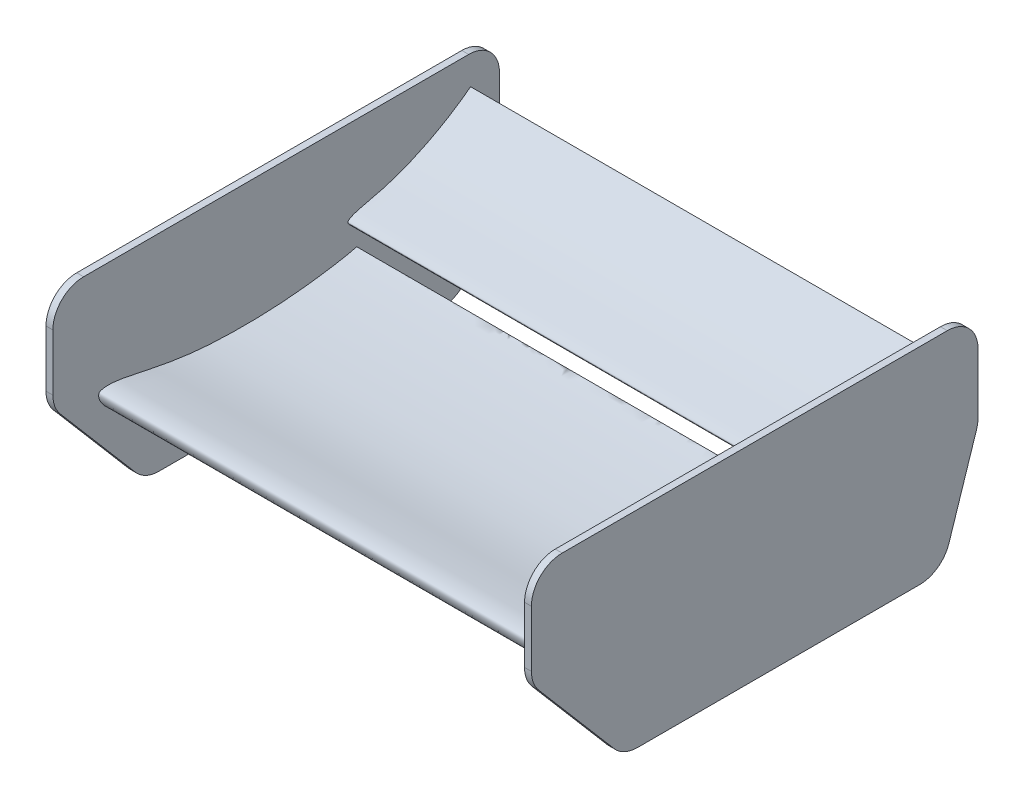
SolidWorks part; units mm, degrees
ref_plane "Front Plane" through (0, 0, 0) normal (0, 0, 1) x (1, 0, 0)
ref_plane "Top Plane" through (0, 0, 0) normal (0, 1, 0) x (1, 0, 0)
ref_plane "Right Plane" through (0, 0, 0) normal (1, 0, 0) x (0, 0, -1)
ref_plane "Soft Top Limit" through (0, 1174.6, 0) normal (0, 1, 0) x (1, 0, 0)
ref_plane "Soft Rear Limit" through (0, 0, -1192.975) normal (0, 0, 1) x (1, 0, 0)
ref_plane "Soft Right Limit" through (-501.65, 0, 0) normal (1, 0, 0) x (0, 0, -1)
ref_plane "Soft Left Limit" through (501.65, 0, 0) normal (1, 0, 0) x (0, 0, -1)
ref_plane "Soft Front Limit" through (0, 0, -165.1) normal (0, 0, 1) x (1, 0, 0)
ref_plane "Slant Limit" through (0, 528.6251, -619.2711) normal (0, -0.6492, 0.7606) x (1, 0, 0)
ref_plane "Bottom" through (0, 476.25, 0) normal (0, 1, 0) x (1, 0, 0)
ref_plane "Midplane" through (0, 0, 0) normal (1, 0, 0) x (0, 0, -1)
curve "Imported Airfoil Curve"
  spline degree 3 poles (0, 2520.0207, 6.126) (0, 2544.889, -1.81) (0, 2521.8965, 7.8839) (0, 2505.3253, 17.7145) (0, 2467.7144, 38.5723) (0, 2424.2142, 62.3813) (0, 2368.0949, 87.8078) (0, 2301.3729, 113.3478) (0, 2223.8362, 140.5377) (0, 2136.6129, 169.2441) (0, 2040.932, 199.097) (0, 1938.2341, 229.6055) (0, 1829.9414, 260.0781) (0, 1717.5266, 289.8586) (0, 1602.4273, 318.1375) (0, 1486.0259, 343.9752) (0, 1369.6902, 366.5754) (0, 1254.3666, 384.7865) (0, 1140.5393, 397.0034) (0, 1028.6357, 403.0127) (0, 919.0585, 402.9406) (0, 812.3986, 397.0375) (0, 709.2785, 385.5985) (0, 610.4299, 369.039) (0, 516.5862, 348.1086) (0, 428.5874, 323.3415) (0, 347.2653, 295.2055) (0, 273.332, 264.2656) (0, 207.4209, 231.0894) (0, 150.0337, 196.3024) (0, 101.596, 160.572) (0, 62.3674, 124.65) (0, 32.4977, 89.3959) (0, 12.0597, 55.6746) (0, 1.683, 26.6201) (0, -0.5567, 6.5526) (0, 0.5894, -3.9947) (0, 1.6947, -9.1451) (0, 2.8711, -12.4915) (0, 3.9449, -14.9776) (0, 4.8993, -16.669) (0, 5.9763, -18.2433) (0, 7.3264, -19.6365) (0, 8.8595, -20.9434) (0, 11.1868, -22.7306) (0, 14.6073, -24.7406) (0, 20.085, -27.4067) (0, 26.8353, -29.9257) (0, 44.6446, -35.1819) (0, 77.8093, -38.8998) (0, 130.2841, -38.2927) (0, 196.3018, -31.4611) (0, 276.2192, -18.4434) (0, 370.8288, 0.8611) (0, 480.7331, 24.811) (0, 605.9792, 50.0099) (0, 745.0759, 74.1542) (0, 895.4497, 95.0846) (0, 1053.6786, 110.004) (0, 1215.6439, 118.3392) (0, 1377.6893, 121.6348) (0, 1537.1174, 120.5125) (0, 1691.5141, 115.2051) (0, 1838.3121, 105.7388) (0, 1975.028, 93.0069) (0, 2099.5942, 78.4581) (0, 2210.5746, 63.1262) (0, 2306.3634, 48.0168) (0, 2387.2069, 33.7158) (0, 2449.0745, 22.0129) (0, 2499.1865, 10.4993) (0, 2520.0207, 6.126) (0, 2544.889, -1.81) (0, 2521.8965, 7.8839) knots -0.016237 -0.007308 -0.001841 0 0.001813 0.006911 0.014576 0.024172 0.035572 0.049013 0.064513 0.081849 0.100772 0.120997 0.142228 0.164173 0.186537 0.209023 0.231367 0.25332 0.274804 0.295858 0.316449 0.336531 0.356033 0.374893 0.39299 0.410197 0.426388 0.441459 0.455334 0.467938 0.479236 0.489204 0.497851 0.505194 0.511308 0.515097 0.516441 0.517273 0.51806 0.518436 0.518797 0.519154 0.519508 0.519887 0.520289 0.52116 0.522116 0.52372 0.525214 0.532575 0.542381 0.554776 0.569931 0.588005 0.609188 0.633329 0.660001 0.688743 0.718873 0.749543 0.780127 0.810209 0.839387 0.867183 0.893104 0.91676 0.937874 0.956199 0.971544 0.983763 0.992692 0.998159 1 1.001813 1.006911 1.014576 periodic
sketch "Airfoils Sketch" plane through (0, 0, 0) normal (1, 0, 0) x (0, 0, -1)
  line L0 (165.1, 1174.6) -> (165.1, 1060.6753) construction
  line L1 (165.1, 1060.6753) -> (663.9798, 476.25) construction
  line L2 (663.9798, 476.25) -> (1192.975, 476.25) construction
  line L3 (1192.975, 476.25) -> (1192.975, 1174.6) construction
  line L4 (1192.975, 1174.6) -> (165.1, 1174.6) construction
  line L5 (509.9361, 1174.6) -> (-509.9361, 1174.6) construction
  line L6 (165.1, 67.0076) -> (165.1, -67.0076) construction
  line L7 (364.7288, 826.8151) -> (873.8134, 230.4351) construction
  line L8 (279.3831, 476.25) -> (-279.3831, 476.25) construction
  line L9 (1192.975, 353.2696) -> (1192.975, -353.2696) construction
  line L10 (364.5896, 498.1423) -> (364.5896, 1393.8577) construction
  line L11 (897.9896, 508.5908) -> (897.9896, 1383.4092) construction
  line L12 (897.9896, 946) -> (364.5896, 946) construction
  line L13 (262.9896, 946) -> (1192.975, 946) construction
  line L14 (855.8887, 1048.5614) -> (904.1623, 945.0386) construction
  line L15 (1108.8736, 1167.1505) -> (1157.6222, 1062.6086) construction
  line L16 (1133.2479, 1114.8795) -> (880.0255, 996.8) construction
  line L17 (219.6255, 996.8) -> (1192.975, 996.8) construction
  line L21 (176.2614, 1047.6) -> (1192.975, 1047.6) construction
  spline S0 degree 3 poles (893.7912, 944.7229) (899.0172, 946.3778) (894.1843, 944.3529) (890.6998, 942.2962) (882.7919, 937.9336) (873.6459, 932.9541) (861.8492, 927.6408) (847.826, 922.3086) (831.5308, 916.6349) (813.2009, 910.6474) (793.0943, 904.4229) (771.5139, 898.0641) (748.7586, 891.7155) (725.138, 885.5141) (700.9544, 879.6292) (676.4985, 874.2577) (652.0578, 869.5659) (627.8318, 865.7954) (603.9228, 863.283) (580.4206, 862.0732) (557.4098, 862.1394) (535.0144, 863.4287) (513.3649, 865.8789) (492.6147, 869.4025) (472.9176, 873.8415) (454.4497, 879.0835) (437.3855, 885.0299) (421.8742, 891.5616) (408.0485, 898.5592) (396.0136, 905.8911) (385.8586, 913.417) (377.6374, 920.9787) (371.3813, 928.3959) (367.1052, 935.4868) (364.9396, 941.5929) (364.4786, 945.8081) (364.7242, 948.0225) (364.9587, 949.1035) (365.2073, 949.8057) (365.434, 950.3273) (365.6352, 950.682) (365.8621, 951.0121) (366.1463, 951.304) (366.4688, 951.5778) (366.9584, 951.952) (367.6776, 952.3725) (368.8291, 952.9298) (370.2479, 953.4556) (373.9902, 954.5511) (380.9564, 955.3164) (391.9757, 955.1645) (405.8359, 953.6991) (422.6123, 950.9282) (442.4709, 946.8302) (465.5393, 941.7496) (491.8288, 936.3995) (521.0273, 931.2645) (552.5956, 926.7991) (585.8161, 923.5923) (619.8244, 921.7664) (653.8518, 920.9989) (687.3317, 921.1602) (719.7569, 922.2028) (750.5884, 924.1223) (779.3042, 926.7322) (805.4694, 929.7293) (828.782, 932.8973) (848.9044, 936.0255) (865.8879, 938.991) (878.8853, 941.4197) (889.4141, 943.8142) (893.7912, 944.7229) (899.0172, 946.3778) (894.1843, 944.3529) knots -0.016237 -0.007308 -0.001841 0 0.001813 0.006911 0.014576 0.024172 0.035572 0.049013 0.064513 0.081849 0.100772 0.120997 0.142228 0.164173 0.186537 0.209023 0.231367 0.25332 0.274804 0.295858 0.316449 0.336531 0.356033 0.374893 0.39299 0.410197 0.426388 0.441459 0.455334 0.467938 0.479236 0.489204 0.497851 0.505194 0.511308 0.515097 0.516441 0.517273 0.51806 0.518436 0.518797 0.519154 0.519508 0.519887 0.520289 0.52116 0.522116 0.52372 0.525214 0.532575 0.542381 0.554776 0.569931 0.588005 0.609188 0.633329 0.660001 0.688743 0.718873 0.749543 0.780127 0.810209 0.839387 0.867183 0.893104 0.91676 0.937874 0.956199 0.971544 0.983763 0.992692 0.998159 1 1.001813 1.006911 1.014576 only from (897.9896, 946) to (897.9896, 946)
  spline S1 degree 3 poles (1131.5375, 1113.3438) (1133.6521, 1115.2864) (1131.806, 1113.2552) (1130.6071, 1111.5075) (1127.8187, 1107.6858) (1124.5791, 1103.2972) (1120.1551, 1098.1634) (1114.6782, 1092.5276) (1108.1983, 1086.2269) (1100.822, 1079.3267) (1092.6546, 1071.9207) (1083.8174, 1064.1247) (1074.4201, 1056.0734) (1064.5795, 1047.9005) (1054.4014, 1039.7532) (1043.9805, 1031.7893) (1033.4164, 1024.1515) (1022.7502, 1016.9986) (1011.956, 1010.5131) (1001.0665, 1004.736) (990.1279, 999.6735) (979.2106, 995.3279) (968.3905, 991.6985) (957.7597, 988.7777) (947.4262, 986.5247) (937.4984, 984.925) (928.0811, 983.9704) (919.2715, 983.6375) (911.1589, 983.8989) (903.8225, 984.7154) (897.3355, 986.0401) (891.7587, 987.81) (887.1468, 989.9462) (883.547, 992.3659) (881.1672, 994.7853) (880.0153, 996.6843) (879.6417, 997.7899) (879.5137, 998.355) (879.4763, 998.7434) (879.4684, 999.0412) (879.4854, 999.2542) (879.52, 999.4611) (879.5903, 999.6626) (879.6829, 999.864) (879.8324, 1000.15) (880.0808, 1000.5088) (880.5041, 1001.0283) (881.0612, 1001.592) (882.5953, 1002.9405) (885.733, 1004.8459) (890.9978, 1007.2132) (897.9021, 1009.5858) (906.4798, 1011.9841) (916.8145, 1014.4348) (928.8905, 1017.1296) (942.5554, 1020.4095) (957.5536, 1024.4354) (973.5286, 1029.3038) (990.0094, 1035.1356) (1006.5584, 1041.7972) (1022.8822, 1048.9655) (1038.7405, 1056.4536) (1053.903, 1064.1266) (1068.1148, 1071.863) (1081.1694, 1079.4589) (1092.9274, 1086.674) (1103.2934, 1093.3387) (1112.1536, 1099.2783) (1119.5597, 1104.4457) (1125.1924, 1108.476) (1129.6607, 1111.9435) (1131.5375, 1113.3438) (1133.6521, 1115.2864) (1131.806, 1113.2552) knots -0.016237 -0.007308 -0.001841 0 0.001813 0.006911 0.014576 0.024172 0.035572 0.049013 0.064513 0.081849 0.100772 0.120997 0.142228 0.164173 0.186537 0.209023 0.231367 0.25332 0.274804 0.295858 0.316449 0.336531 0.356033 0.374893 0.39299 0.410197 0.426388 0.441459 0.455334 0.467938 0.479236 0.489204 0.497851 0.505194 0.511308 0.515097 0.516441 0.517273 0.51806 0.518436 0.518797 0.519154 0.519508 0.519887 0.520289 0.52116 0.522116 0.52372 0.525214 0.532575 0.542381 0.554776 0.569931 0.588005 0.609188 0.633329 0.660001 0.688743 0.718873 0.749543 0.780127 0.810209 0.839387 0.867183 0.893104 0.91676 0.937874 0.956199 0.971544 0.983763 0.992692 0.998159 1 1.001813 1.006911 1.014576 only from (1133.2479, 1114.8795) to (1133.2479, 1114.8795)
  dimension "D1" = 533.4
  dimension "D2" = 228.6
  dimension "D3" = 0
  dimension "D4" = 101.6
  dimension "D5" = 279.4
  dimension "D6" = 177.8
  dimension "D7" = 25
  dimension "D8" = 660.4
extrude "Extruded Airfoils" add sketch "Airfoils Sketch" along normal offset from surface (487.45 mm away) 14.2 up to plane "Soft Left Limit"
sketch "Endplate Sketch" plane through (501.65, 0, 0) normal (1, 0, 0) x (0, 0, -1)
  line L6 (333.4477, 1174.6) -> (1129.475, 1174.6)
  line L7 (1192.975, 1174.6) -> (165.1, 1174.6) construction
  line L8 (1192.975, 1111.1) -> (1192.975, 986.6717)
  line L9 (1192.975, 476.25) -> (1192.975, 1174.6) construction
  line L11 (1189.8464, 966.9854) -> (1132.8969, 792.34)
  line L12 (1072.5255, 748.5263) -> (489.1772, 748.5263)
  line L19 (440.8805, 770.7991) -> (285.151, 953.2323)
  line L26 (269.9477, 994.4595) -> (269.9477, 1111.1)
  line L28 (165.1, 1060.6753) -> (663.9798, 476.25) construction
  arc A12 (1129.475, 1174.6) -> (1192.975, 1111.1) centre (1129.475, 1111.1) cw
  arc A13 (1192.975, 986.6717) -> (1189.8464, 966.9854) centre (1129.475, 986.6717) cw
  arc A14 (1132.8969, 792.34) -> (1072.5255, 748.5263) centre (1072.5255, 812.0263) cw
  arc A15 (489.1772, 748.5263) -> (440.8805, 770.7991) centre (489.1772, 812.0263) cw
  arc A16 (285.151, 953.2323) -> (269.9477, 994.4595) centre (333.4477, 994.4595) cw
  arc A17 (333.4477, 1174.6) -> (269.9477, 1111.1) centre (333.4477, 1111.1) ccw
  point P16 (1192.975, 1174.6)
  point P19 (1192.975, 976.5799)
  point P29 (269.9477, 1174.6)
  dimension "D1" = 63.5
extrude "Extruded Endplate" add sketch "Endplate Sketch" against normal up to surface (14.2 mm away)
mirror "Mirror" about plane through (0, 0, 0) normal (1, 0, 0) of bodies 106
